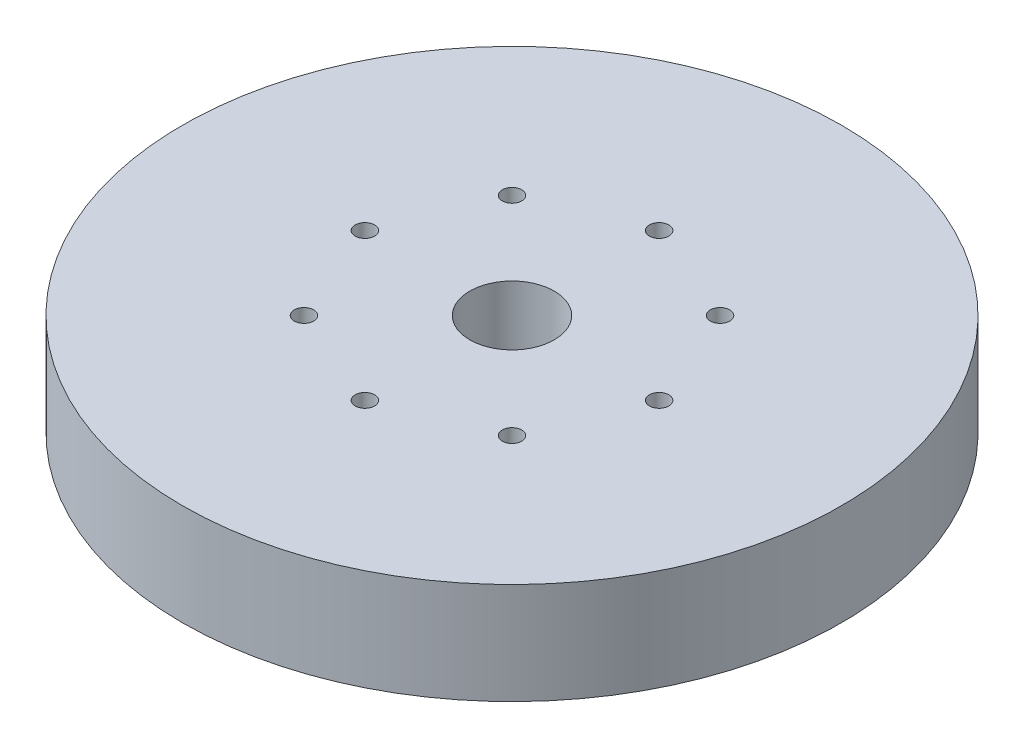
SolidWorks part; units mm, degrees
ref_plane "Front Plane" through (0, 0, 0) normal (0, 0, 1) x (1, 0, 0)
ref_plane "Top Plane" through (0, 0, 0) normal (0, 1, 0) x (1, 0, 0)
ref_plane "Right Plane" through (0, 0, 0) normal (1, 0, 0) x (0, 0, -1)
sketch "Sketch1" plane through (0, 0, 0) normal (0, 1, 0) x (1, 0, 0)
  circle A0 centre (0, 0) radius 97.5
  dimension "FLANGE_OD" = 195
extrude "Boss-Extrude1" add sketch "Sketch1" along normal blind 30
sketch "Sketch2" plane through (0, 0, 0) normal (0, 1, 0) x (1, 0, 0)
  circle A0 centre (0, 0) radius 12.5
  dimension "BORE_D" = 25
extrude "Cut-Extrude1" cut sketch "Sketch2" along normal through all
sketch "Sketch3" plane through (0, 30, 0) normal (0, 1, 0) x (1, 0, 0)
  circle A0 centre (0, 0) radius 43.5222 construction
  circle A1 centre (-43.5222, 0) radius 2.8757
  dimension "BOLT_D" = 5.7514
  dimension "BOLT_PCD" = 87.0443
extrude "Cut-Extrude2" cut sketch "Sketch3" against normal blind 22.5859
pattern_circular "CirPattern1" count 8 over 360 about axis through (0, 0, 0) along (0, 1, 0) of "Cut-Extrude2"
